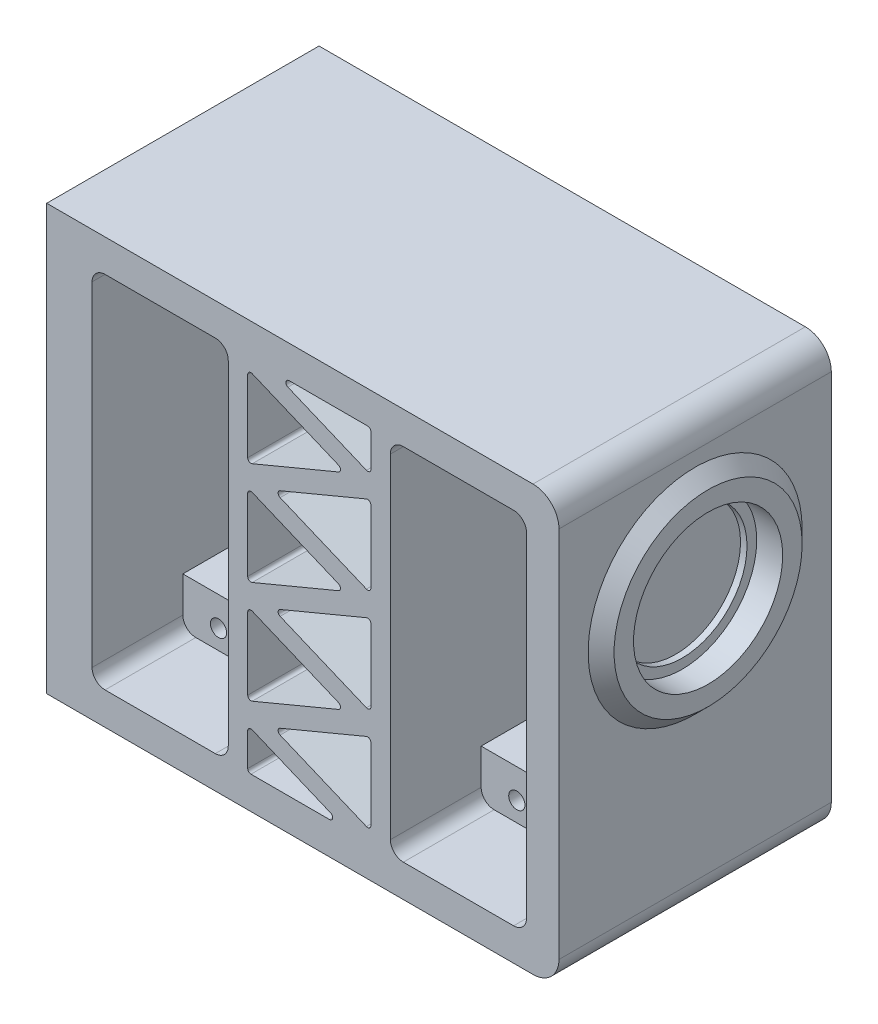
SolidWorks part; units mm, degrees
ref_plane "Front Plane" through (0, 0, 0) normal (0, 0, 1) x (1, 0, 0)
ref_plane "Top Plane" through (0, 0, 0) normal (0, 1, 0) x (1, 0, 0)
ref_plane "Right Plane" through (0, 0, 0) normal (1, 0, 0) x (0, 0, -1)
sketch "Sketch1" plane through (0, 0, 0) normal (0, 0, 1) x (1, 0, 0)
  line L0 (5, 60.5) -> (26, 60.5)
  line L1 (0, 0) -> (77, 0)
  line L2 (0, 0) -> (0, 65.5)
  line L3 (0, 65.5) -> (77, 65.5)
  line L4 (77, 0) -> (77, 65.5)
  line L5 (51, 60.5) -> (72, 60.5)
  line L6 (51, 60.5) -> (51, 5)
  line L7 (51, 5) -> (72, 5)
  line L8 (72, 60.5) -> (72, 5)
  line L9 (5, 60.5) -> (5, 5)
  line L10 (5, 5) -> (26, 5)
  line L12 (26, 60.5) -> (26, 5)
  line L13 (5, 53) -> (26, 53)
  line L14 (51, 53) -> (72, 53)
  line L15 (5, 12.5) -> (26, 12.5)
  line L16 (51, 12.5) -> (72, 12.5)
  line L17 (10.5, 57.5) -> (20.5, 57.5) construction
  line L18 (10.5, 8) -> (20.5, 8) construction
  line L19 (15.5, 57.5) -> (15.5, 8) construction
  line L20 (5, 32.75) -> (26, 32.75) construction
  line L21 (51, 32.75) -> (72, 32.75) construction
  line L22 (61.5, 57.5) -> (61.5, 8) construction
  line L23 (56.5, 57.5) -> (66.5, 57.5) construction
  line L24 (56.5, 8) -> (66.5, 8) construction
  circle A0 centre (10.5, 57.5) radius 1.25
  circle A1 centre (20.5, 57.5) radius 1.25
  circle A2 centre (10.5, 8) radius 1.25
  circle A3 centre (20.5, 8) radius 1.25
  circle A4 centre (56.5, 57.5) radius 1.25
  circle A5 centre (66.5, 57.5) radius 1.25
  circle A6 centre (66.5, 8) radius 1.25
  circle A7 centre (56.5, 8) radius 1.25
  point P33 (15.5, 32.75)
  point P34 (15.5, 32.75)
  point P41 (61.5, 32.75)
  point P42 (61.5, 32.75)
  point P53 (61.5, 8)
  point P55 (61.5, 57.5)
  dimension "D13" = 2.5
  dimension "D1" = 21
  dimension "D2" = 5
  dimension "D3" = 55.5
  dimension "D4" = 55.5
  dimension "D5" = 21
  dimension "D6" = 5
  dimension "D7" = 5
  dimension "D8" = 25
  dimension "D9" = 5
  dimension "D10" = 7.5
  dimension "D11" = 7.5
  dimension "D12" = 10
  dimension "D15" = 49.5
extrude "Boss-Extrude2" add sketch "Sketch1" against normal blind 28 contours L1 L4 L3 L2 L5 L8 L7 L6 L0 L12 L10 L9 | L9 L13 L12 L0 | L15 L9 L10 L12 | L16 L6 L7 L8 | L6 L14 L8 L5 | A0 | A1 | A4 | A5 | A6 | A7 | A3 | A2 region at (15.5, 56.7001, 0) region at (15.5, 8.7999, 0) region at (38.5, 32.75, 0) region at (61.5, 56.7001, 0) region at (61.5, 8.7999, 0) region at (10.5, 57.5, 0) region at (20.5, 57.5, 0) region at (56.5, 57.5, 0) region at (66.5, 57.5, 0) region at (66.5, 8, 0) region at (56.5, 8, 0)
extrude "Boss-Extrude4" add sketch "Sketch1<4>" along normal blind 14 contours L1 L4 L3 L2 L5 L8 L7 L6 L0 L12 L10 L9 region at (38.5, 32.75, 0)
sketch "Sketch1<4>" plane through (0, 0, 0) normal (0, 0, 1) x (1, 0, 0) same geometry as "Sketch1"
extrude "Cut-Extrude1" cut sketch "Sketch1<5>" against normal blind 12 contours A0 | A2 | A3 | A7 | A6 | A4 | A1 | A5 region at (10.5, 57.5, 0) region at (10.5, 8, 0) region at (20.5, 8, 0) region at (56.5, 57.5, 0) region at (66.5, 8, 0) region at (56.5, 8, 0)
sketch "Sketch1<5>" plane through (0, 0, 0) normal (0, 0, 1) x (1, 0, 0) same geometry as "Sketch1"
sketch "Sketch5" plane through (0, 0, 14) normal (0, 0, 1) x (1, 0, 0)
  line L0 (28.4223, 59.1157) -> (44.105, 52.5714)
  line L1 (26, 5) -> (51, 5)
  line L2 (26, 5) -> (26, 60.5)
  line L3 (26, 60.5) -> (51, 60.5)
  line L4 (51, 5) -> (51, 60.5)
  line L5 (26, 60.5) -> (26, 5) construction
  line L6 (51, 60.5) -> (51, 5) construction
  line L7 (5, 60.5) -> (26, 60.5) construction
  line L8 (5, 5) -> (26, 5) construction
  line L9 (29, 60.5) -> (48, 60.5)
  line L10 (48, 5) -> (48, 60.5)
  line L11 (29, 5) -> (48, 5)
  line L12 (29, 5) -> (29, 60.5)
  line L13 (29, 60.5) -> (48, 52.5714)
  line L14 (48, 52.5714) -> (29, 44.6429)
  line L15 (29, 44.6429) -> (48, 36.7143)
  line L16 (48, 36.7143) -> (29, 28.7857)
  line L17 (29, 28.7857) -> (48, 20.8571)
  line L18 (48, 20.8571) -> (29, 12.9286)
  line L19 (29, 12.9286) -> (48, 5)
  line L20 (44.105, 52.5714) -> (25.105, 44.6429)
  line L21 (25.105, 44.6429) -> (44.105, 36.7143)
  line L22 (44.105, 36.7143) -> (25.105, 28.7857)
  line L23 (25.105, 28.7857) -> (44.105, 20.8571)
  line L24 (44.105, 20.8571) -> (25.105, 12.9286)
  line L25 (25.105, 12.9286) -> (47.4223, 3.6157)
  line L26 (29.5777, 61.8843) -> (51.895, 52.5714)
  line L27 (51.895, 52.5714) -> (32.895, 44.6429)
  line L28 (32.895, 44.6429) -> (51.895, 36.7143)
  line L29 (51.895, 36.7143) -> (32.895, 28.7857)
  line L30 (32.895, 28.7857) -> (51.895, 20.8571)
  line L31 (51.895, 20.8571) -> (32.895, 12.9286)
  line L32 (32.895, 12.9286) -> (48.5777, 6.3843)
  dimension "D2" = 1.5
  dimension "D1" = 3
  dimension "D4" = 3
  dimension "D3" = 1.5
extrude "Cut-Extrude2" cut sketch "Sketch5" against normal through all contours L20 L0 L12 | L9 L26 L10 | L27 L28 L10 | L22 L21 L12 | L29 L30 L10 | L24 L23 L12 | L31 L32 L10 | L25 L12 L11 region at (34.035, 52.5714, 14) region at (42.965, 58.3989, 14) region at (34.035, 36.7143, 14) region at (42.965, 44.6429, 14) region at (42.965, 28.7857, 14) region at (34.035, 20.8571, 14) region at (42.965, 12.9286, 14) region at (34.035, 7.1011, 14)
fillet "Fillet4" radius 0.5 24 edges at (44.105, 5, -7) (29, 11.3032, -7) (29, 5, -7) (48, 6.6254, -7) (48, 19.2318, -7) (32.895, 12.9286, -7) (29, 14.5539, -7) (29, 27.1604, -7) (44.105, 20.8571, -7) (48, 22.4825, -7) (48, 35.0889, -7) (32.895, 28.7857, -7) (44.105, 36.7143, -7) (29, 30.4111, -7) (29, 43.0175, -7) (48, 38.3396, -7) (32.895, 44.6429, -7) (48, 50.9461, -7) (29, 46.2682, -7) (44.105, 52.5714, -7) (29, 58.8746, -7) (48, 54.1968, -7) (48, 60.5, -7) (32.895, 60.5, -7)
sketch "Sketch8" plane through (0, 12.5, 0) normal (0, 1, 0) x (1, 0, 0)
  line L0 (26, 28) -> (26, 0) construction
  line L1 (5, 28) -> (26, 28)
  line L2 (5, 28) -> (5, 8)
  line L3 (5, 8) -> (26, 8)
  line L4 (26, 28) -> (26, 8)
  line L5 (51, 0) -> (72, 0) construction
  line L6 (51, 28) -> (72, 28)
  line L7 (51, 28) -> (51, 8)
  line L8 (51, 8) -> (72, 8)
  line L9 (72, 28) -> (72, 8)
  line L10 (72, 28) -> (72, 0) construction
  dimension "D1" = 8
extrude "Cut-Extrude8" cut sketch "Sketch8" against normal blind 10
ref_plane "Midplane" through (0, 32.75, 0) normal (0, 1, 0) x (1, 0, 0)
ref_plane "Plane2" through (61.5, 0, 0) normal (1, 0, 0) x (0, 0, -1)
ref_plane "Plane3" through (15.5, 0, 0) normal (1, 0, 0) x (0, 0, -1)
sketch "Sketch10" plane through (61.5, 0, 0) normal (1, 0, 0) x (0, 0, -1)
  line L0 (28, 2.5) -> (8, 2.5) construction
  line L1 (8, 2.5) -> (8, 12.5) construction
  line L2 (28, 2.5) -> (8, 2.5)
  line L3 (8, 2.5) -> (8, 12.5)
  line L4 (8, 12.5) -> (18, 2.5)
  dimension "D1" = 45
extrude "Boss-Extrude5" add sketch "Sketch10" along normal blind 1.5 and the other way blind 1.5 contours L4 L3 L2 region at (61.5, 5.8333, -11.3333)
sketch "Sketch11" plane through (15.5, 0, 0) normal (1, 0, 0) x (0, 0, -1)
  line L0 (28, 2.5) -> (8, 2.5) construction
  line L1 (8, 2.5) -> (8, 12.5) construction
  line L2 (28, 2.5) -> (8, 2.5)
  line L3 (8, 2.5) -> (8, 12.5)
  line L4 (8, 12.5) -> (18, 2.5)
  dimension "D1" = 45
extrude "Boss-Extrude6" add sketch "Sketch11" along normal blind 1.5 and the other way blind 1.5 contours L4 L3 L2 region at (15.5, 5.8333, -11.3333)
mirror "Mirror2" about plane through (0, 32.75, 0) normal (0, 1, 0) of "Boss-Extrude6", "Boss-Extrude5", "Cut-Extrude8"
sketch "Sketch13" plane through (0, 0, 0) normal (-1, 0, 0) x (0, 0, 1)
  line L4 (-28, 0) -> (14, 0)
  line L5 (14, 0) -> (14, 65.5)
  line L6 (14, 65.5) -> (-28, 65.5)
  line L7 (-28, 65.5) -> (-28, 0)
  line L8 (-28, 0) -> (14, 0)
  line L9 (14, 0) -> (14, 65.5)
  line L10 (14, 65.5) -> (-28, 65.5)
  line L11 (-28, 65.5) -> (-28, 0)
  dimension "D1" = 0
extrude "Boss-Extrude7" add sketch "Sketch13" along normal blind 2
fillet "Fillet3" radius 2 16 edges at (51, 60.5, 7) (72, 5, 7) (72, 60.5, 7) (51, 5, 7) (5, 5, 7) (26, 5, 7) (26, 60.5, 7) (5, 60.5, 7) (72, 63, -18) (72, 2.5, -18) (51, 2.5, -18) (51, 63, -18) (26, 63, -18) (26, 2.5, -18) (5, 63, -18) (5, 2.5, -18)
sketch "Sketch14" plane through (-2, 0, 0) normal (-1, 0, 0) x (0, 0, 1)
  line L8 (-24, 61.5) -> (-24, 4)
  line L9 (-24, 4) -> (10, 4)
  line L10 (10, 4) -> (10, 61.5)
  line L11 (10, 61.5) -> (-24, 61.5)
  line L12 (-24, 61.5) -> (-24, 4) construction
  line L13 (-24, 4) -> (10, 4) construction
  line L14 (10, 4) -> (10, 61.5) construction
  line L15 (10, 61.5) -> (-24, 61.5) construction
  circle A0 centre (-24, 61.5) radius 1.25
  circle A1 centre (10, 61.5) radius 1.25
  circle A2 centre (10, 4) radius 1.25
  circle A3 centre (-24, 4) radius 1.25
  dimension "D2" = 2.5
  dimension "D1" = 4
extrude "Cut-Extrude9" cut sketch "Sketch14" against normal blind 7
fillet "Fillet7" radius 4 2 edges at (77, 65.5, -7) (77, 0, -7)
sketch "Sketch15" plane through (77, 0, 0) normal (1, 0, 0) x (0, 0, -1)
  line L0 (-14, 32.75) -> (28, 32.75) construction
  line L1 (-14, 4) -> (-14, 61.5) construction
  line L2 (28, 4) -> (28, 61.5) construction
  line L3 (-14, 42.75) -> (28, 42.75) construction
  circle A0 centre (7, 42.75) radius 13.5
  dimension "D2" = 27
  dimension "D1" = 10
extrude "Boss-Extrude8" add sketch "Sketch15" along normal blind 2
sketch "Sketch16" plane through (79, 0, 0) normal (1, 0, 0) x (0, 0, -1)
  circle A0 centre (7, 42.75) radius 11.5
  dimension "D1" = 23
extrude "Cut-Extrude10" cut sketch "Sketch16" against normal blind 4
chamfer "Chamfer1" distance 3 angle 45 1 edges at (77, 42.75, -20.5)
sketch "Sketch17" plane through (75, 0, 0) normal (1, 0, 0) x (0, 0, -1)
  circle A0 centre (7, 42.75) radius 10
  dimension "D1" = 20
extrude "Cut-Extrude11" cut sketch "Sketch17" against normal blind 1
